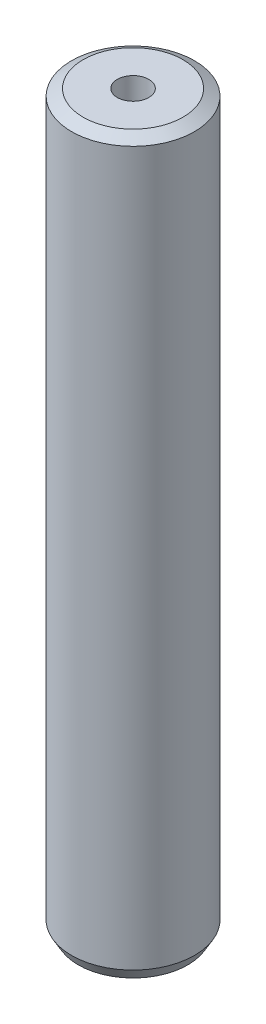
SolidWorks part; units mm, degrees
ref_plane "Front Plane" through (0, 0, 0) normal (0, 0, 1) x (1, 0, 0)
ref_plane "Top Plane" through (0, 0, 0) normal (0, 1, 0) x (1, 0, 0)
ref_plane "Right Plane" through (0, 0, 0) normal (1, 0, 0) x (0, 0, -1)
sketch "Sketch1" plane through (0, 0, 0) normal (0, 1, 0) x (1, 0, 0)
  circle A0 centre (0, 0) radius 7.5
  dimension "SHAFT_OD" = 15
extrude "Boss-Extrude1" add sketch "Sketch1" along normal blind 89.2455
sketch "Sketch2" plane through (0, 0, 0) normal (0, 1, 0) x (1, 0, 0)
  circle A0 centre (0, 0) radius 1.9214
  dimension "BORE_D" = 3.8428
extrude "Cut-Extrude1" cut sketch "Sketch2" along normal through all
chamfer "Chamfer1" distance 0.8156 angle 60 2 edges at (0, 89.2455, 7.5) (0, 0, 7.5) first distance on face at (0, 89.2455, 7.5) first distance on face at (0, 0, 1.9214)
